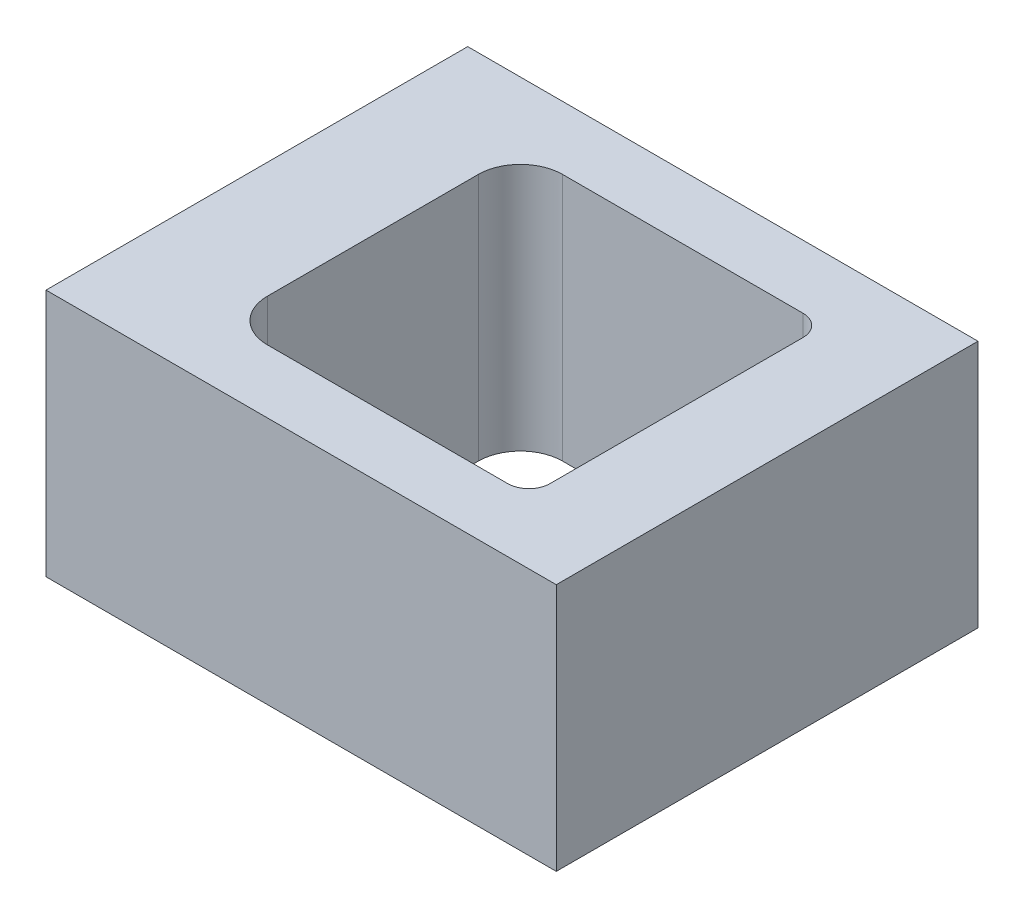
SolidWorks part; units mm, degrees
ref_plane "Front Plane" through (0, 0, 0) normal (0, 0, 1) x (1, 0, 0)
ref_plane "Top Plane" through (0, 0, 0) normal (0, 1, 0) x (1, 0, 0)
ref_plane "Right Plane" through (0, 0, 0) normal (1, 0, 0) x (0, 0, -1)
sketch "Sketch1" plane through (0, 0, 0) normal (0, 1, 0) x (1, 0, 0)
  line L1 (-88.265, -63.5) -> (65.405, -63.5)
  line L2 (-88.265, -63.5) -> (-88.265, 63.5)
  line L3 (-88.265, 63.5) -> (65.405, 63.5)
  line L4 (65.405, -63.5) -> (65.405, 63.5)
  line L5 (-88.265, -63.5) -> (65.405, 63.5) construction
  line L6 (-88.265, 63.5) -> (65.405, -63.5) construction
  line L22 (65.405, 0) -> (38.1, 0) construction
  line L23 (38.1, 38.1) -> (38.1, -38.1) construction
  line L27 (-53.34, 31.75) -> (-53.34, -31.75)
  line L28 (-40.64, -44.45) -> (31.75, -44.45)
  line L29 (38.1, -38.1) -> (38.1, 38.1)
  line L30 (31.75, 44.45) -> (-40.64, 44.45)
  line L31 (-53.34, 31.75) -> (-53.34, -31.75)
  line L32 (-40.64, -44.45) -> (31.75, -44.45)
  line L33 (38.1, -38.1) -> (38.1, 38.1)
  line L34 (31.75, 44.45) -> (-40.64, 44.45)
  arc A28 (-40.64, 44.45) -> (-53.34, 31.75) centre (-40.64, 31.75) ccw
  arc A29 (-40.64, 44.45) -> (-53.34, 31.75) centre (-40.64, 31.75) ccw
  arc A30 (-53.34, -31.75) -> (-40.64, -44.45) centre (-40.64, -31.75) ccw
  arc A31 (-53.34, -31.75) -> (-40.64, -44.45) centre (-40.64, -31.75) ccw
  arc A32 (31.75, -44.45) -> (38.1, -38.1) centre (31.75, -38.1) ccw
  arc A33 (31.75, -44.45) -> (38.1, -38.1) centre (31.75, -38.1) ccw
  arc A34 (38.1, 38.1) -> (31.75, 44.45) centre (31.75, 38.1) ccw
  arc A35 (38.1, 38.1) -> (31.75, 44.45) centre (31.75, 38.1) ccw
  point P0 (38.1, 0)
  dimension "D1" = 127
  dimension "D2" = 153.67
  dimension "D3" = 0
  dimension "D4" = 27.305
extrude "Boss-Extrude1" add sketch "Sketch1" along normal offset from surface (74.7776 mm away) 73.1774
